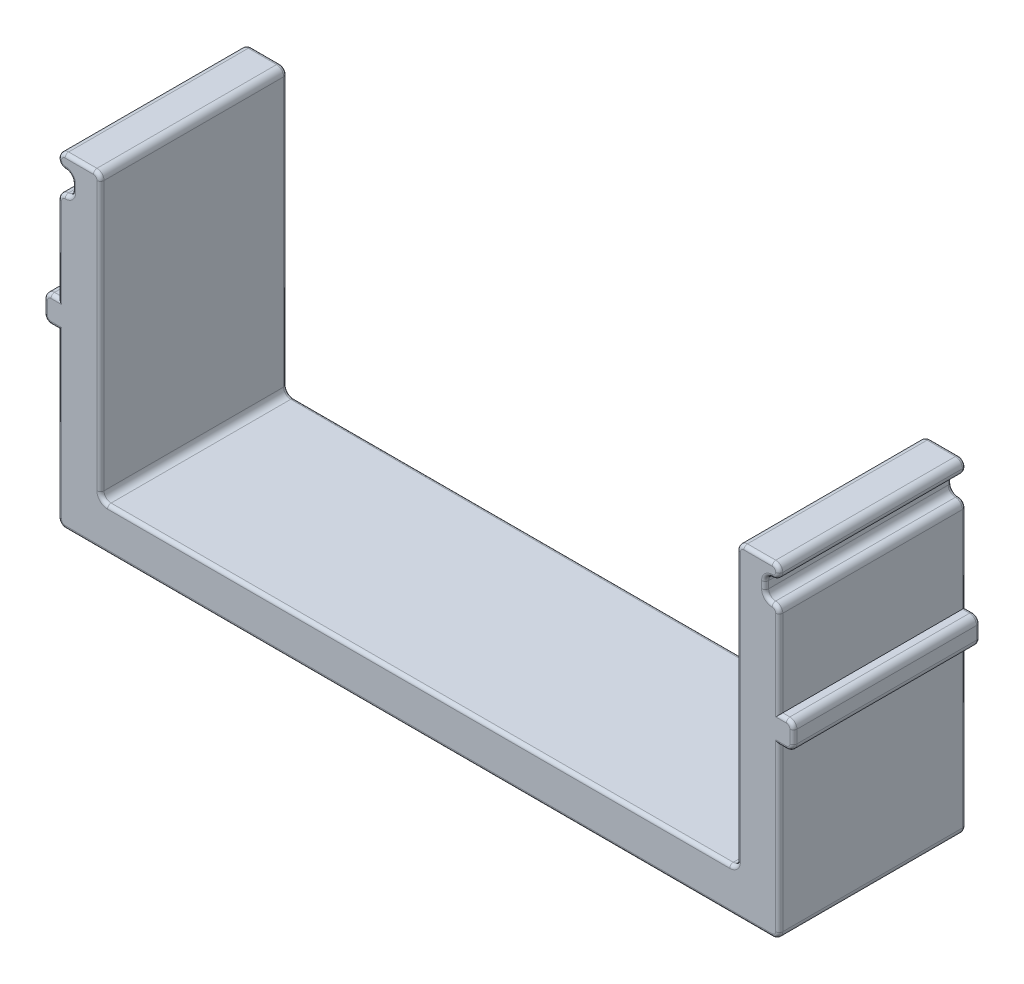
SolidWorks part; units mm, degrees
ref_plane "Front Plane" through (0, 0, 0) normal (0, 0, 1) x (1, 0, 0)
ref_plane "Top Plane" through (0, 0, 0) normal (0, 1, 0) x (1, 0, 0)
ref_plane "Right Plane" through (0, 0, 0) normal (1, 0, 0) x (0, 0, -1)
sketch "Sketch1" plane through (0, 0, 0) normal (0, 0, 1) x (1, 0, 0)
  line L0 (0, 1) -> (0, 16.3582) construction
  line L1 (25.5, -2) -> (-25.5, -2)
  line L2 (-25.5, -2) -> (-25.5, 10)
  line L3 (-25.5, 10) -> (-26.5, 10)
  line L4 (-26.5, 10) -> (-26.5, 11.9)
  line L5 (-26.5, 11.9) -> (-25.5, 11.9)
  line L6 (-25.5, 11.9) -> (-25.5, 18.5)
  line L7 (-25.5, 18.5) -> (-24.5, 18.5)
  line L8 (-24.5, 18.5) -> (-24.5, 20)
  line L9 (-24.5, 20) -> (-25.5, 20)
  line L10 (-25.5, 20) -> (-25.5, 21)
  line L11 (-25.5, 21) -> (-22.5, 21)
  line L12 (-22.5, 21) -> (-22.5, 1)
  line L13 (-22.5, 1) -> (22.5, 1)
  line L15 (25.5, -2) -> (25.5, 10)
  line L16 (25.5, 10) -> (26.5, 10)
  line L17 (26.5, 10) -> (26.5, 11.9)
  line L18 (26.5, 11.9) -> (25.5, 11.9)
  line L19 (25.5, 11.9) -> (25.5, 18.5)
  line L20 (25.5, 18.5) -> (24.5, 18.5)
  line L21 (24.5, 18.5) -> (24.5, 20)
  line L22 (24.5, 20) -> (25.5, 20)
  line L23 (25.5, 20) -> (25.5, 21)
  line L24 (25.5, 21) -> (22.5, 21)
  line L25 (22.5, 21) -> (22.5, 1)
  dimension "D1" = 1.9
  dimension "D2" = 3
  dimension "D3" = 3
  dimension "D4" = 1
  dimension "D6" = 25.5
  dimension "D7" = 12
  dimension "D8" = 1
  dimension "D9" = 3
  dimension "D10" = 23
  dimension "D11" = 1
  dimension "D12" = 1.5
extrude "Boss-Extrude1" add sketch "Sketch1" along normal blind 13.2
fillet "Fillet1" radius 0.5 20 edges at (-25.5, 21, 6.6) (-25.5, 20, 6.6) (-24.5, 20, 6.6) (-25.5, 18.5, 6.6) (-24.5, 18.5, 6.6) (25.5, 18.5, 6.6) (24.5, 18.5, 6.6) (24.5, 20, 6.6) (25.5, 20, 6.6) (25.5, 21, 6.6) (-22.5, 21, 6.6) (22.5, 21, 6.6) (22.5, 1, 6.6) (-22.5, 1, 6.6) (25.5, -2, 6.6) (-25.5, -2, 6.6) (-26.5, 10, 6.6) (-26.5, 11.9, 6.6) (26.5, 10, 6.6) (26.5, 11.9, 6.6)
fillet "Fillet2" radius 0.25 76 edges at (-25.75, 11.9, 13.2) (-26.3536, 11.7536, 13.2) (-25.75, 10, 13.2) (-26.3536, 10.1464, 13.2) (-25.75, 11.9, 0) (-26.3536, 11.7536, 0) (-25.75, 10, 0) (-26.3536, 10.1464, 0) (25.75, 10, 13.2) (26.3536, 10.1464, 13.2) (25.75, 11.9, 13.2) (26.3536, 11.7536, 13.2) (25.75, 10, 0) (26.3536, 10.1464, 0) (25.75, 11.9, 0) (26.3536, 11.7536, 0) (-25.5, 14.95, 0) (-25.3536, 18.3536, 0) (-24.6464, 18.6464, 0) (-24.5, 19.25, 0) (-24.6464, 19.8536, 0) (-25.3536, 20.1464, 0) (-25.3536, 20.8536, 0) (-24, 21, 0) (-22.6464, 20.8536, 0) (-22.5, 11, 0) (-22.3536, 1.1464, 0) (0, 1, 0) (22.3536, 1.1464, 0) (22.5, 11, 0) (22.6464, 20.8536, 0) (24, 21, 0) (25.3536, 20.8536, 0) (25.3536, 20.1464, 0) (24.6464, 19.8536, 0) (24.5, 19.25, 0) (24.6464, 18.6464, 0) (25.3536, 18.3536, 0) (-25.5, 4.25, 0) (-25.3536, -1.8536, 0) (0, -2, 0) (25.3536, -1.8536, 0) (-25.5, 14.95, 13.2) (-25.3536, 18.3536, 13.2) (-24.6464, 18.6464, 13.2) (-24.5, 19.25, 13.2) (-24.6464, 19.8536, 13.2) (-25.3536, 20.1464, 13.2) (-25.3536, 20.8536, 13.2) (-24, 21, 13.2) (-22.6464, 20.8536, 13.2) (-22.5, 11, 13.2) (-22.3536, 1.1464, 13.2) (0, 1, 13.2) (22.3536, 1.1464, 13.2) (22.5, 11, 13.2) (22.6464, 20.8536, 13.2) (24, 21, 13.2) (25.3536, 20.8536, 13.2) (25.3536, 20.1464, 13.2) (24.6464, 19.8536, 13.2) (24.5, 19.25, 13.2) (24.6464, 18.6464, 13.2) (25.3536, 18.3536, 13.2) (-25.5, 4.25, 13.2) (-25.3536, -1.8536, 13.2) (0, -2, 13.2) (25.3536, -1.8536, 13.2) (-26.5, 10.95, 13.2) (-26.5, 10.95, 0) (26.5, 10.95, 13.2) (26.5, 10.95, 0) (25.5, 14.95, 0) (25.5, 4.25, 0) (25.5, 14.95, 13.2) (25.5, 4.25, 13.2)
